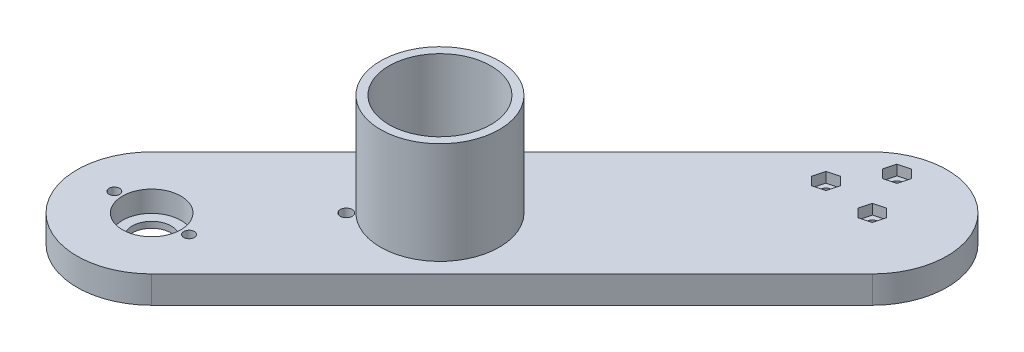
SolidWorks part; units mm, degrees
ref_plane "Front Plane" through (0, 0, 0) normal (0, 0, 1) x (1, 0, 0)
ref_plane "Top Plane" through (0, 0, 0) normal (0, 1, 0) x (1, 0, 0)
ref_plane "Right Plane" through (0, 0, 0) normal (1, 0, 0) x (0, 0, -1)
sketch "Sketch1" plane through (0, 0, 0) normal (0, 1, 0) x (1, 0, 0)
  line L0 (0, 0) -> (106.066, 106.066) construction
  line L25 (-15.5563, 15.5563) -> (90.5097, 121.6224)
  line L26 (15.5563, -15.5563) -> (121.6224, 90.5097)
  line L27 (106.066, 106.066) -> (-3.1733, 182.5562) construction
  line L28 (97.4624, 93.7787) -> (-11.777, 170.269)
  line L29 (114.6697, 118.3533) -> (5.4303, 194.8435)
  line L30 (99.7189, 119.6662) -> (91.1152, 107.3789) construction
  line L31 (106.9626, 109.4121) -> (103.6165, 108.5155)
  line L32 (103.6165, 108.5155) -> (102.72, 105.1694)
  line L33 (102.72, 105.1694) -> (105.1694, 102.72)
  line L34 (105.1694, 102.72) -> (108.5155, 103.6165)
  line L35 (108.5155, 103.6165) -> (109.4121, 106.9626)
  line L36 (109.4121, 106.9626) -> (106.9626, 109.4121)
  line L37 (97.2329, 93.4511) -> (-12.0064, 169.9413)
  line L38 (90.2186, 104.0328) -> (93.5647, 104.9294)
  line L39 (93.5647, 104.9294) -> (94.4613, 108.2754)
  line L40 (94.4613, 108.2754) -> (92.0118, 110.7249)
  line L41 (92.0118, 110.7249) -> (88.6657, 109.8284)
  line L42 (88.6657, 109.8284) -> (87.7692, 106.4823)
  line L43 (87.7692, 106.4823) -> (90.2186, 104.0328)
  line L44 (100.6154, 123.0122) -> (97.2694, 122.1156)
  line L45 (97.2694, 122.1156) -> (96.3728, 118.7696)
  line L46 (96.3728, 118.7696) -> (98.8223, 116.3201)
  line L47 (98.8223, 116.3201) -> (102.1684, 117.2167)
  line L48 (102.1684, 117.2167) -> (103.0649, 120.5627)
  line L49 (103.0649, 120.5627) -> (100.6154, 123.0122)
  line L66 (114.8991, 118.681) -> (5.6597, 195.1712)
  arc A12 (-15.5563, 15.5563) -> (15.5563, -15.5563) centre (0, 0) ccw
  arc A13 (121.6224, 90.5097) -> (90.5097, 121.6224) centre (106.066, 106.066) ccw
  arc A14 (97.4624, 93.7787) -> (114.6697, 118.3533) centre (106.066, 106.066) ccw
  arc A15 (5.4303, 194.8435) -> (-11.777, 170.269) centre (-3.1733, 182.5562) ccw
  circle A16 centre (106.066, 106.066) radius 1.7
  circle A17 centre (106.066, 106.066) radius 3 construction
  circle A18 centre (99.7189, 119.6662) radius 1.7
  circle A19 centre (91.1152, 107.3789) radius 1.7
  circle A20 centre (91.1152, 107.3789) radius 3 construction
  circle A21 centre (99.7189, 119.6662) radius 3 construction
  arc A22 (5.6597, 195.1712) -> (-12.0064, 169.9413) centre (-3.1733, 182.5562) ccw
  arc A23 (97.2329, 93.4511) -> (114.8991, 118.681) centre (106.066, 106.066) ccw
  point P14 (53.033, 53.033)
  point P50 (51.4463, 144.3111)
  point P66 (95.417, 113.5225)
  dimension "D17" = 15
  dimension "D18" = 3.4
  dimension "D19" = 6
  dimension "D20" = 3.4
  dimension "D22" = 3.4
  dimension "D23" = 6
  dimension "D24" = 6
  dimension "D14" = 45
  dimension "D15" = 150
  dimension "D16" = 80
  dimension "D21" = 15
  dimension "D25" = 13
  dimension "D26" = 0.4
extrude "Boss-Extrude1" add sketch "Sketch1" along normal blind 8 contours L26 A13 L25 A12
sketch "Sketch4" plane through (0, 0, 0) normal (0, 1, 0) x (1, 0, 0)
  line L0 (-11, 0) -> (11, 0) construction
  line L7 (0, 0) -> (106.066, 106.066) construction
  line L48 (42.4264, 50.4264) -> (42.4264, 34.4264) construction
  line L49 (42.4264, 42.4264) -> (0, 0) construction
  circle A0 centre (42.4264, 42.4264) radius 15
  circle A18 centre (42.4264, 50.4264) radius 1.1
  circle A19 centre (42.4264, 34.4264) radius 1.1
  circle A21 centre (42.4264, 42.4264) radius 5.75
  circle A22 centre (0, 0) radius 8.6
  circle A23 centre (0, 0) radius 5.75
  circle A24 centre (-11, 0) radius 1.55
  circle A25 centre (11, 0) radius 1.55
  circle A26 centre (0, 0) radius 32.5 construction
  circle A27 centre (42.4264, 42.4264) radius 17.5
  circle A28 centre (28.6378, 28.6378) radius 1.75
  point P59 (0, 0)
  dimension "D3" = 60
  dimension "D4" = 2.2
  dimension "D5" = 16
  dimension "D6" = 11.5
  dimension "D7" = 2.2
  dimension "D10" = 40.5
  dimension "D11" = 3.5
  dimension "D8" = 30
  dimension "D9" = 35
  dimension "D18" = 11.5
  dimension "D19" = 17.2
  dimension "D20" = 3.1
  dimension "D21" = 3.1
  dimension "D23" = 65
  dimension "D22" = 22
extrude "Boss-Extrude3" add sketch "Sketch4" along normal blind 30 from surface contours A27 A0 starting at face at (53.033, 8, -53.033)
extrude "Cut-Extrude9" cut sketch "Sketch4<5>" along normal through all both and the other way through all contours A23 | A21 | A18 | A19 | A28 region at (42.4264, 0, -50.4264) region at (42.4264, 0, -34.4264) region at (42.4264, 0, -42.4264) region at (0, 0, 0) region at (28.6378, 0, -28.6378)
sketch "Sketch4<5>" plane through (0, 0, 0) normal (0, 1, 0) x (1, 0, 0) same geometry as "Sketch4"
extrude "Cut-Extrude5" cut sketch "Sketch1<8>" against normal blind 3 from surface contours L48 L49 L44 L45 L46 L47 A18 | L42 L43 L38 L39 L40 L41 A19 | L35 L36 L31 L32 L33 L34 A16 region at (108.1204, 0, -108.1204) region at (89.0608, 0, -105.3245) region at (101.7733, 0, -121.7206) starting at face at (0, 8, 5.75)
sketch "Sketch1<8>" plane through (0, 0, 0) normal (0, 1, 0) x (1, 0, 0) same geometry as "Sketch1"
extrude "Cut-Extrude6" cut sketch "Sketch1<9>" along normal blind 3 from surface contours L66 A22 L37 A23 starting at face at (0, 0, 5.75)
sketch "Sketch1<9>" plane through (0, 0, 0) normal (0, 1, 0) x (1, 0, 0) same geometry as "Sketch1"
extrude "Cut-Extrude11" cut sketch "Sketch4<7>" against normal blind 6.2 from surface contours A22 A23 | A25 | A24 region at (-8.3568, 0, 0) region at (-11, 0, 0) region at (11, 0, 0) starting at face at (91.1152, 8, -107.3789)
sketch "Sketch4<7>" plane through (0, 0, 0) normal (0, 1, 0) x (1, 0, 0) same geometry as "Sketch4"
extrude "Cut-Extrude13" cut sketch "Sketch1<10>" along normal through all both and the other way through all contours A18 | A19 | A16 region at (106.066, 0, -106.066) region at (99.7189, 0, -119.6662) region at (91.1152, 0, -107.3789)
sketch "Sketch1<10>" plane through (0, 0, 0) normal (0, 1, 0) x (1, 0, 0) same geometry as "Sketch1"
extrude "Cut-Extrude14" cut sketch "Sketch4<8>" against normal blind 6 from surface contours A0 starting at face at (42.4264, 8, -49.3264)
sketch "Sketch4<8>" plane through (0, 0, 0) normal (0, 1, 0) x (1, 0, 0) same geometry as "Sketch4"
